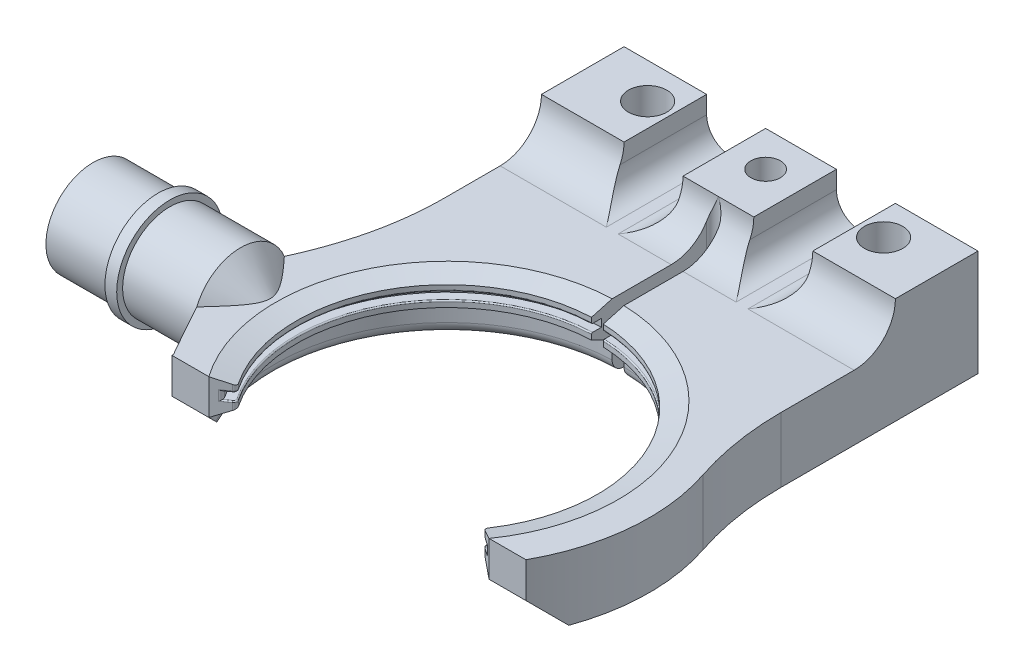
SolidWorks part; units mm, degrees
ref_plane "Front Plane" through (0, 0, 0) normal (0, 0, 1) x (1, 0, 0)
ref_plane "Top Plane" through (0, 0, 0) normal (0, 1, 0) x (1, 0, 0)
ref_plane "Right Plane" through (0, 0, 0) normal (1, 0, 0) x (0, 0, -1)
sketch "Sketch1" plane through (0, 0, 0) normal (0, 0, 1) x (1, 0, 0)
  line L0 (0, 0) -> (0, 15.868) construction
  line L1 (-27.2, -0.2693) -> (-27.2, 1.0307)
  line L2 (-27.2, 1.0307) -> (-25.5, 1.0307)
  line L3 (-25.5, 1.0307) -> (-25.5, 2.0307)
  line L4 (-25.5, 2.0307) -> (-29, 3)
  line L5 (-29, 3) -> (-29, -3)
  line L6 (-29, -3) -> (-25.5, -1.3298)
  line L7 (-27.2, -0.2693) -> (-25.5, -0.2693)
  line L8 (-25.5, -0.2693) -> (-25.5, -1.3298)
  point P13 (-27.2, 0.3807)
  dimension "D1" = 1.7
  dimension "D2" = 25.5
  dimension "D3" = 3.5
  dimension "D4" = 0
  dimension "D5" = 3
  dimension "D6" = 3
  dimension "D7" = 1.3
  dimension "D8" = 74.521
  dimension "D9" = 64.49
  dimension "D10" = 1
revolve "Revolve1" add sketch "Sketch1" angle 360 about L0
sketch "Sketch2" plane through (0, 0, 0) normal (0, 1, 0) x (1, 0, 0)
  line L0 (0, 0) -> (-45.0147, -31.5197)
  line L1 (0, 0) -> (44.1827, -30.9371)
  line L2 (0, 0) -> (0, -13.7284) construction
  line L3 (-45.0147, -31.5197) -> (44.1827, -30.9371)
  dimension "D1" = 55
  dimension "D2" = 55
extrude "Cut-Extrude1" cut sketch "Sketch2" against normal through all and the other way through all
sketch "Sketch3" plane through (0, 0, 0) normal (0, 1, 0) x (1, 0, 0)
  line L0 (-30, -16.6337) -> (-30, 60)
  line L1 (-30, 60) -> (30, 60)
  line L3 (-30, -16.6337) -> (-23.7554, -16.6337)
  line L4 (30, -16.6337) -> (23.7554, -16.6337)
  line L5 (30, 60) -> (30, 16.6337)
  arc A0 (23.7554, -16.6337) -> (-23.7554, -16.6337) centre (0, 0) ccw
  circle A1 centre (0, 54) radius 2.5
  circle A2 centre (-20, 54) radius 3.25
  circle A3 centre (20, 54) radius 3.25
  arc A4 (23.7554, -16.6337) -> (-23.7554, -16.6337) centre (0, 0) ccw construction
  arc A5 (30, -16.6337) -> (30, 16.6337) centre (0, 0) ccw
  point P18 (0, 60)
  dimension "D8" = 6.5
  dimension "D9" = 6.5
  dimension "D10" = 5
  dimension "D2" = 20
  dimension "D3" = 6
  dimension "D4" = 60
  dimension "D5" = 20
  dimension "D6" = 60
extrude "Boss-Extrude1" add sketch "Sketch3" along normal blind 3 and the other way blind 8 contours L1 L0 A3 A2 A1 region at (1.2898, 0, -36.2025)
sketch "Sketch4" plane through (0, 0, 0) normal (0, 1, 0) x (1, 0, 0)
  line L1 (-30, 60) -> (30, 60)
  line L2 (-30, 60) -> (-30, 46)
  line L3 (-30, 46) -> (30, 46)
  line L4 (30, 60) -> (30, 46)
  line L5 (30, 60) -> (30, 16.6337) construction
  circle A0 centre (-20, 54) radius 3.25 construction
  circle A1 centre (-20, 54) radius 3.25
  circle A2 centre (0, 54) radius 2.5 construction
  circle A3 centre (0, 54) radius 2.5
  circle A4 centre (20, 54) radius 3.25 construction
  circle A5 centre (20, 54) radius 3.25
  dimension "D1" = 14
extrude "Boss-Extrude2" add sketch "Sketch4" along normal blind 10
fillet "Fillet1" radius 7 1 edges at (0, 3, -46)
sketch "Sketch5" plane through (0, 0, 0) normal (0, 1, 0) x (1, 0, 0)
  line L0 (0, 45) -> (0, -0.8023) construction
  line L1 (1, 45) -> (1, -0.8023)
  line L2 (-1, 45) -> (-1, -0.8023)
  arc A0 (1, 45) -> (-1, 45) centre (0, 45) ccw
  arc A1 (-1, -0.8023) -> (1, -0.8023) centre (0, -0.8023) ccw
  point P3 (0, 22.0988)
  dimension "D1" = 45
  dimension "D3" = 1
  dimension "D2" = 22.0988
extrude "Cut-Extrude2" cut sketch "Sketch5" against normal through all and the other way through all
sketch "Sketch6" plane through (0, 0, 0) normal (0, 1, 0) x (1, 0, 0)
  line L0 (30, 60) -> (-30, 60) construction
  line L1 (-4.1548, 72.2673) -> (4.1548, 72.2673)
  line L2 (-4.1548, 72.2673) -> (-4.1548, 47.7327)
  line L3 (-4.1548, 47.7327) -> (4.1548, 47.7327)
  line L4 (4.1548, 72.2673) -> (4.1548, 47.7327)
  line L5 (-4.1548, 72.2673) -> (4.1548, 47.7327) construction
  line L6 (-4.1548, 47.7327) -> (4.1548, 72.2673) construction
  point P0 (0, 60)
extrude "Cut-Extrude3" cut sketch "Sketch6" along normal blind 4
sketch "Sketch7" plane through (0, 0, 0) normal (0, 1, 0) x (1, 0, 0)
  line L1 (-16, 66.549) -> (-6, 66.549)
  line L2 (-16, 66.549) -> (-16, 20)
  line L3 (-16, 20) -> (-6, 20)
  line L4 (-6, 66.549) -> (-6, 20)
  line L6 (6, 66.549) -> (16, 66.549)
  line L7 (6, 66.549) -> (6, 20)
  line L8 (6, 20) -> (16, 20)
  line L9 (16, 66.549) -> (16, 20)
  point P6 (6, 43.2745)
  point P7 (-11, 20)
  dimension "D1" = 6
  dimension "D2" = 6
  dimension "D3" = 10
  dimension "D4" = 10
  dimension "D5" = 20
  dimension "D6" = 20
extrude "Cut-Extrude4" cut sketch "Sketch7" against normal blind 7 from offset 10
fillet "Fillet2" radius 4 4 edges at (6, 3, -49.5) (16, 3, -49.5) (-6, 3, -49.5) (-16, 3, -49.5)
fillet "Fillet3" radius 0.6 6 edges at (20.8884, 1.5307, 14.6262) (22.2809, 0.3807, 15.6013) (20.8884, -0.7995, 14.6262) (-20.8884, -0.7995, 14.6262) (-20.8884, 1.5307, 14.6262) (-22.2809, 0.3807, 15.6013)
sketch "Sketch9" plane through (0, 0, 0) normal (1, 0, 0) x (0, 0, -1)
  circle A0 centre (0, 0) radius 8
  dimension "D1" = 0
  dimension "D2" = 16
extrude "Boss-Extrude5" add sketch "Sketch9" against normal blind 30 from surface starting at face at (-30, 1.425, -28.8637)
chamfer "Chamfer2" distance 5 angle 45 1 edges at (-30, 8, 0)
sketch "Sketch10" plane through (-60, 0, 0) normal (-1, 0, 0) x (0, 0, 1)
  circle A0 centre (0, 0) radius 4.5
  dimension "D1" = 9
fillet "Fillet11" radius 0.2 12 edges at (-22.0707, 1.0307, 15.454) (-21.1287, 1.0307, 14.5859) (-22.0707, -0.2693, 15.454) (-21.1287, -0.2693, 14.5859) (22.0707, 1.0307, 15.454) (21.1287, 1.0307, 14.5859) (22.0707, -0.2693, 15.454) (21.1287, -0.2693, 14.5859) (-22.7136, 1.0307, -11.5906) (-22.7136, -0.2693, -11.5906) (22.7136, 1.0307, -11.5906) (22.7136, -0.2693, -11.5906)
sketch "Sketch15" plane through (-60, 0, 0) normal (-1, 0, 0) x (0, 0, 1)
  circle A0 centre (0, 0) radius 9
  circle A1 centre (0, 0) radius 8 construction
  dimension "D1" = 1
extrude "Boss-Extrude15" add sketch "Sketch15" against normal blind 2 from offset 11 offset against normal yes
chamfer "Chamfer4" distance 5 angle 60 2 edges at (-30, -4.4721, 6.6332) (-30, -4.4721, -6.6332) first distance on face at (-32, 1.0111, 0)
fillet "Fillet33" radius 50 1 edges at (-30, -2.6527, -16.4477)
chamfer "Chamfer3" distance 5 angle 45 2 edges at (26.8777, -8, 16.6337) (-26.8777, -8, 16.6337)
fillet "Fillet32" radius 2 3 edges at (-24.5432, -8, -15.4476) (25.2837, -5.4304, 14.2033) (24.5432, -8, -15.4476)
fillet "Fillet34" radius 50 1 edges at (30, -2.5, -16.6337)
